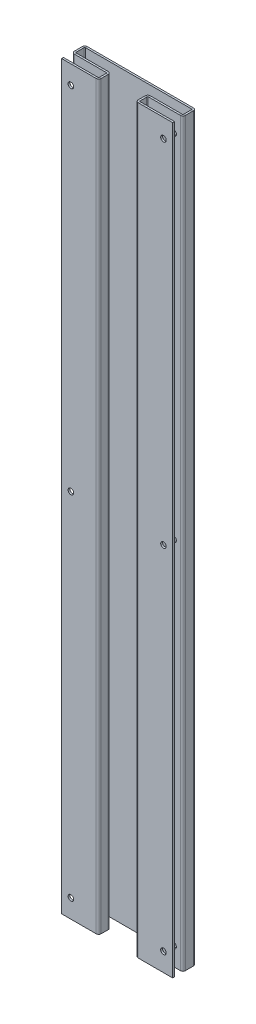
SolidWorks part; units mm, degrees
note: The reader was unsure of these and kept them because the rebuilt part matched: thickness of "Base-Flange1", "Edge-Flange1", "Edge-Flange2", "Edge-Flange3", "Edge-Flange4", "Sheet-Metal1", "Sheet-Metal2", "Sheet-Metal3", "Sheet-Metal4", "Sheet-Metal5"; flange length of "Edge-Flange1", "Edge-Flange2", "Edge-Flange3", "Edge-Flange4".
material "2024-O"
ref_plane "Front Plane" through (0, 0, 0) normal (0, 0, 1) x (1, 0, 0)
ref_plane "Top Plane" through (0, 0, 0) normal (0, 1, 0) x (1, 0, 0)
ref_plane "Right Plane" through (0, 0, 0) normal (1, 0, 0) x (0, 0, -1)
sketch "Sketch1" plane through (0, 0, 0) normal (0, 0, 1) x (1, 0, 0)
  line L1 (20, -400) -> (-20, -400)
  line L2 (20, -400) -> (20, 400)
  line L3 (20, 400) -> (-20, 400)
  line L4 (-20, -400) -> (-20, 400)
  line L5 (20, -400) -> (-20, 400) construction
  line L6 (20, 400) -> (-20, -400) construction
  point P0 (0, 0)
  dimension "D1" = 800
  dimension "D2" = 40
base flange "Base-Flange1" sketch "Sketch1" thickness 2 reverse thickness direction no parameters "D1"=0.7366
edge flange "Edge-Flange1" sketch "Sketch8" flange angle 90 flange length 13 flange position material inside bend radius 0.7366 thickness 2 relief rectangular parameters "D6"=10
sketch "Sketch8" plane through (20, 0, -2) normal (1, 0, 0) x (0, -1, 0)
  line L2 (-400, 0) -> (-400, 11)
  line L3 (-400, 11) -> (400, 11)
  line L4 (400, 11) -> (400, 0)
  line L7 (400, 0) -> (-400, 0) construction
  line L8 (400, 0) -> (-400, 0)
bend "EdgeBend1" bend radius 0.7366 bend angle 90 parameters "D5"=1
edge flange "Edge-Flange2" sketch "Sketch11" flange angle 90 flange length 40 flange position material inside bend radius 0.7366 thickness 2 relief rectangular parameters "D6"=10
sketch "Sketch11" plane through (18, 0, -13) normal (0, 0, -1) x (0, -1, 0)
  line L2 (-400, 0) -> (-400, 38)
  line L3 (-400, 38) -> (400, 38)
  line L4 (400, 38) -> (400, 0)
  line L7 (400, 0) -> (-400, 0) construction
  line L8 (400, 0) -> (-400, 0)
bend "EdgeBend2" bend radius 0.7366 bend angle 90 parameters "D5"=2
edge flange "Edge-Flange3" sketch "Sketch14" flange angle 90 flange length 14 flange position material inside bend radius 0.7366 thickness 2 relief rectangular parameters "D6"=10
sketch "Sketch14" plane through (-20, 0, -13) normal (-1, 0, 0) x (0, 1, 0)
  line L2 (-400, 0) -> (-400, 12)
  line L3 (-400, 12) -> (400, 12)
  line L4 (400, 12) -> (400, 0)
  line L11 (-400, 0) -> (400, 0) construction
  line L12 (-400, 0) -> (400, 0)
bend "EdgeBend3" bend radius 0.7366 bend angle 90 parameters "D5"=3
edge flange "Edge-Flange4" sketch "Sketch17" flange angle 90 flange length 60 flange position material inside bend radius 0.7366 thickness 2 relief rectangular parameters "D6"=10
sketch "Sketch17" plane through (-18, 0, -25) normal (0, 0, -1) x (0, 1, 0)
  line L0 (400, 0) -> (-400, 0) construction
  line L1 (400, 0) -> (-400, 0)
  line L2 (-400, 0) -> (-400, 58)
  line L3 (-400, 58) -> (400, 58)
  line L4 (400, 58) -> (400, 0)
bend "EdgeBend4" bend radius 0.7366 bend angle 90 parameters "D5"=4
mirror "Mirror2" about plane through (40, -400, -25) normal (-1, 0, 0) of bodies 105
bend "MirrorBend3" bend radius 0.7366 bend angle 90 parameters "D5"=7
bend "MirrorBend4" bend radius 0.7366 bend angle 90 parameters "D5"=8
bend "MirrorBend5" bend radius 0.7366 bend angle 90 parameters "D5"=11
bend "MirrorBend6" bend radius 0.7366 bend angle 90 parameters "D5"=12
sketch "Sketch18" plane through (0, 0, -25) normal (0, 0, -1) x (-1, 0, 0)
  line L0 (7.2634, -390) -> (7.2634, 390) construction
  line L2 (17.2634, 400) -> (17.2634, -400) construction
  line L3 (17.2634, 400) -> (-97.2634, 400) construction
  line L4 (-97.2634, -400) -> (17.2634, -400) construction
  circle A0 centre (7.2634, -390) radius 5
  dimension "D4" = 10
  dimension "D1" = 10
  dimension "D2" = 10
  dimension "D3" = 10
sketch "Sketch20" plane through (0, 0, 0) normal (0, 0, 1) x (1, 0, 0)
  circle A0 centre (90, 0) radius 3 construction
  circle A1 centre (90, 380) radius 3 construction
  circle A2 centre (90, -380) radius 3 construction
  circle A3 centre (90, 0) radius 3
  circle A4 centre (90, 380) radius 3
  circle A5 centre (90, -380) radius 3
  circle A6 centre (-10, -380) radius 3 construction
  circle A7 centre (-10, 0) radius 3 construction
  circle A8 centre (-10, 380) radius 3 construction
  circle A9 centre (-10, -380) radius 3
  circle A10 centre (-10, 0) radius 3
  circle A11 centre (-10, 380) radius 3
extrude "Cut-Extrude1" cut sketch "Sketch20" against normal through all normal cut yes
sketch "Bend-Lines1" [suppressed] plane through (0, 0, 0) normal (0, 1, 0) x (1, 0, 0)
sketch "Bounding-Box1" [suppressed] plane through (0, 0, 0) normal (0, 1, 0) x (1, 0, 0)
sheet metal parameters "Sheet-Metal1" thickness 2 parameters "D1"=0.7366
flat pattern "Flat-Pattern1" [suppressed]
sketch "Bend-Lines2" plane through (0, 0, 0) normal (0, 1, 0) x (1, 0, 0)
sketch3d "Bounding-Box2" [suppressed]
  line L0 (-50, 400, 0) -> (-50, -400, 0) construction
  line L1 (50, 400, 0) -> (50, -400, 0) construction
  line L2 (-50, 400, 0) -> (50, 400, 0) construction
  line L3 (-50, -400, 0) -> (50, -400, 0) construction
sheet metal parameters "Sheet-Metal2" thickness 2 parameters "D1"=0.7366, "D7"=0.5
flat pattern "Flat-Pattern1"
sketch "Bend-Lines2" plane through (0, 0, 0) normal (0, 0, 1) x (1, 0, 0)
  line L0 (17.1091, -400) -> (17.1091, 400) construction
  line L1 (17.1091, -400) -> (17.1091, 400) construction
sketch3d "Bounding-Box2" [suppressed]
  line L0 (22.2181, 400, 0) -> (22.2181, -400, 0) construction
  line L1 (-20, 400, 0) -> (-20, -400, 0) construction
  line L2 (22.2181, 400, 0) -> (-20, 400, 0) construction
  line L3 (22.2181, -400, 0) -> (-20, -400, 0) construction
bend of the flat pattern "Flatten-<EdgeBend1>1"
sheet metal parameters "Sheet-Metal3" thickness 2 parameters "D1"=0.7366, "D7"=0.5
flat pattern "Flat-Pattern1" [suppressed]
sketch "Bend-Lines2" plane through (0, 0, 0) normal (0, 0, 1) x (1, 0, 0)
  line L0 (49.5383, -400) -> (49.5383, 400) construction
  line L1 (49.5383, -400) -> (49.5383, 400) construction
  line L2 (58.6148, -400) -> (58.6148, 400) construction
  line L3 (58.6148, -400) -> (58.6148, 400) construction
sketch3d "Bounding-Box2" [suppressed]
  line L0 (78.1531, 400, 0) -> (78.1531, -400, 0) construction
  line L1 (-50, 400, 0) -> (-50, -400, 0) construction
  line L2 (78.1531, 400, 0) -> (-50, 400, 0) construction
  line L3 (78.1531, -400, 0) -> (-50, -400, 0) construction
bend of the flat pattern "Flatten-<EdgeBend1>1"
bend of the flat pattern "Flatten-<EdgeBend2>1"
sheet metal parameters "Sheet-Metal4" thickness 2 parameters "D1"=0.7366, "D7"=0.5
flat pattern "Flat-Pattern1" [suppressed]
sketch "Bend-Lines2" plane through (0, 0, 0) normal (0, 0, 1) x (1, 0, 0)
  line L0 (49.5383, -400) -> (49.5383, 400) construction
  line L1 (49.5383, -400) -> (49.5383, 400) construction
  line L2 (58.6148, -400) -> (58.6148, 400) construction
  line L3 (58.6148, -400) -> (58.6148, 400) construction
  line L4 (77.6914, -400) -> (77.6914, 400) construction
  line L5 (77.6914, -400) -> (77.6914, 400) construction
sketch3d "Bounding-Box2" [suppressed]
  line L0 (97.2296, 400, 0) -> (97.2296, -400, 0) construction
  line L1 (-50, 400, 0) -> (-50, -400, 0) construction
  line L2 (97.2296, 400, 0) -> (-50, 400, 0) construction
  line L3 (97.2296, -400, 0) -> (-50, -400, 0) construction
bend of the flat pattern "Flatten-<EdgeBend3>1"
bend of the flat pattern "Flatten-<EdgeBend1>1"
bend of the flat pattern "Flatten-<EdgeBend2>1"
sheet metal parameters "Sheet-Metal5" thickness 2 parameters "D1"=0.7366, "D7"=0.5
flat pattern "Flat-Pattern1" [suppressed]
sketch "Bend-Lines2" plane through (0, 0, 0) normal (0, 0, 1) x (1, 0, 0)
  line L0 (24.5383, -400) -> (24.5383, 400) construction
  line L1 (24.5383, -400) -> (24.5383, 400) construction
  line L2 (33.6148, -400) -> (33.6148, 400) construction
  line L3 (33.6148, -400) -> (33.6148, 400) construction
  line L4 (52.6914, -400) -> (52.6914, 400) construction
  line L5 (52.6914, -400) -> (52.6914, 400) construction
  line L6 (71.7679, -400) -> (71.7679, 400) construction
  line L7 (71.7679, -400) -> (71.7679, 400) construction
sketch3d "Bounding-Box2" [suppressed]
  line L0 (121.3062, 400, 0) -> (121.3062, -400, 0) construction
  line L1 (-25, 400, 0) -> (-25, -400, 0) construction
  line L2 (121.3062, 400, 0) -> (-25, 400, 0) construction
  line L3 (121.3062, -400, 0) -> (-25, -400, 0) construction
bend of the flat pattern "Flatten-<EdgeBend3>1"
bend of the flat pattern "Flatten-<EdgeBend4>1"
bend of the flat pattern "Flatten-<EdgeBend1>1"
bend of the flat pattern "Flatten-<EdgeBend2>1"
sheet metal parameters "Sheet-Metal6" thickness 0.5 parameters "D1"=0.7366
flat pattern "Flat-Pattern6" [suppressed]
sketch "Bend-Lines3" plane through (0, 0, 0) normal (0, 0, 1) x (1, 0, 0)
  line L0 (194.6459, -400) -> (194.6459, 400) construction
  line L1 (205.9005, -400) -> (205.9005, 400) construction
  line L4 (77.3913, -400) -> (77.3913, 400) construction
  line L5 (66.1366, -400) -> (66.1366, 400) construction
  line L6 (28.882, -400) -> (28.882, 400) construction
  line L7 (18.6273, -400) -> (18.6273, 400) construction
  line L8 (194.6459, -400) -> (194.6459, 400) construction
  line L9 (205.9005, -400) -> (205.9005, 400) construction
  line L12 (77.3913, -400) -> (77.3913, 400) construction
  line L13 (66.1366, -400) -> (66.1366, 400) construction
  line L14 (28.882, -400) -> (28.882, 400) construction
  line L15 (18.6273, -400) -> (18.6273, 400) construction
  line L16 (243.1552, -400) -> (243.1552, 400) construction
  line L17 (253.4098, -400) -> (253.4098, 400) construction
  line L18 (243.1552, -400) -> (243.1552, 400) construction
  line L19 (253.4098, -400) -> (253.4098, 400) construction
sketch3d "Bounding-Box3" [suppressed]
  line L0 (292.0372, 400, 0) -> (292.0372, -400, 0) construction
  line L1 (-20, 400, 0) -> (-20, -400, 0) construction
  line L2 (292.0372, 400, 0) -> (-20, 400, 0) construction
  line L3 (292.0372, -400, 0) -> (-20, -400, 0) construction
bend of the flat pattern "Flatten-<EdgeBend4>2"
bend of the flat pattern "Flatten-<EdgeBend3>2"
bend of the flat pattern "Flatten-<MirrorBend3>1"
bend of the flat pattern "Flatten-<MirrorBend4>1"
bend of the flat pattern "Flatten-<EdgeBend1>2"
bend of the flat pattern "Flatten-<EdgeBend2>2"
bend of the flat pattern "Flatten-<MirrorBend5>1"
bend of the flat pattern "Flatten-<MirrorBend6>1"
sketch "Sketch18-1" [suppressed] plane through (96.0186, 0, -2) normal (0, 0, -1) x (-1, 0, 0)
  line L0 (7.2634, -390) -> (7.2634, 390) construction
  line L2 (17.2634, 400) -> (17.2634, -400) construction
  line L3 (116.0186, 400) -> (-196.0186, 400) construction
  line L4 (-196.0186, -400) -> (116.0186, -400) construction
  circle A0 centre (7.2634, -390) radius 5
  dimension "D4" = 10
  dimension "D1" = 10
  dimension "D2" = 10
  dimension "D3" = 10
sheet metal parameters "Sheet-Metal7" thickness 0.5 parameters "D1"=0.7366
flat pattern "Flat-Pattern6" [suppressed]
sketch "Bend-Lines3" plane through (0, 0, 0) normal (0, 0, 1) x (1, 0, 0)
  line L0 (194.6459, -400) -> (194.6459, 400) construction
  line L1 (205.9005, -400) -> (205.9005, 400) construction
  line L4 (77.3913, -400) -> (77.3913, 400) construction
  line L5 (66.1366, -400) -> (66.1366, 400) construction
  line L6 (28.882, -400) -> (28.882, 400) construction
  line L7 (18.6273, -400) -> (18.6273, 400) construction
  line L8 (194.6459, -400) -> (194.6459, 400) construction
  line L9 (205.9005, -400) -> (205.9005, 400) construction
  line L12 (77.3913, -400) -> (77.3913, 400) construction
  line L13 (66.1366, -400) -> (66.1366, 400) construction
  line L14 (28.882, -400) -> (28.882, 400) construction
  line L15 (18.6273, -400) -> (18.6273, 400) construction
  line L16 (243.1552, -400) -> (243.1552, 400) construction
  line L17 (253.4098, -400) -> (253.4098, 400) construction
  line L18 (243.1552, -400) -> (243.1552, 400) construction
  line L19 (253.4098, -400) -> (253.4098, 400) construction
sketch3d "Bounding-Box3" [suppressed]
  line L0 (292.0372, 400, 0) -> (292.0372, -400, 0) construction
  line L1 (-20, 400, 0) -> (-20, -400, 0) construction
  line L2 (292.0372, 400, 0) -> (-20, 400, 0) construction
  line L3 (292.0372, -400, 0) -> (-20, -400, 0) construction
bend of the flat pattern "Flatten-<EdgeBend4>2"
bend of the flat pattern "Flatten-<EdgeBend3>2"
bend of the flat pattern "Flatten-<MirrorBend3>1"
bend of the flat pattern "Flatten-<MirrorBend4>1"
bend of the flat pattern "Flatten-<EdgeBend1>2"
bend of the flat pattern "Flatten-<EdgeBend2>2"
bend of the flat pattern "Flatten-<MirrorBend5>1"
bend of the flat pattern "Flatten-<MirrorBend6>1"
sketch "Sketch18-1" [suppressed] plane through (96.0186, 0, -2) normal (0, 0, -1) x (-1, 0, 0)
  line L0 (7.2634, -390) -> (7.2634, 390) construction
  line L2 (17.2634, 400) -> (17.2634, -400) construction
  line L3 (116.0186, 400) -> (-196.0186, 400) construction
  line L4 (-196.0186, -400) -> (116.0186, -400) construction
  circle A0 centre (7.2634, -390) radius 5
  dimension "D4" = 10
  dimension "D1" = 10
  dimension "D2" = 10
  dimension "D3" = 10
